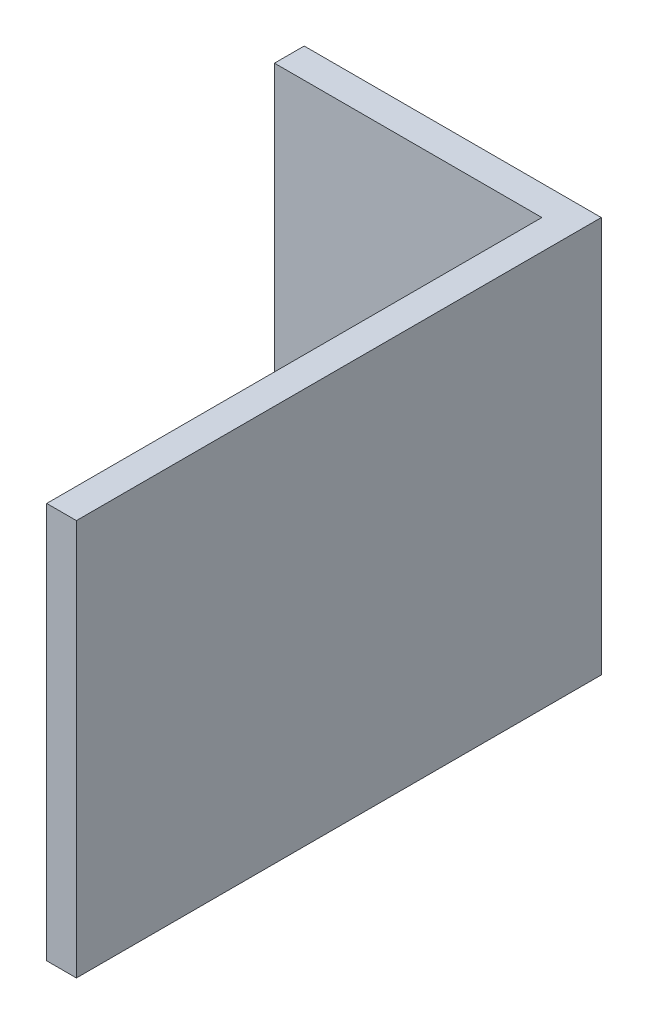
SolidWorks part; units mm, degrees
ref_plane "Plano frontal" through (0, 0, 0) normal (0, 0, 1) x (1, 0, 0)
ref_plane "Plano superior" through (0, 0, 0) normal (0, 1, 0) x (1, 0, 0)
ref_plane "Plano direito" through (0, 0, 0) normal (1, 0, 0) x (0, 0, -1)
sketch "Esboço1" plane through (0, 0, 0) normal (0, 1, 0) x (1, 0, 0)
  line L0 (0, 0) -> (30, 0)
  line L1 (30, 0) -> (30, -53)
  line L2 (30, -53) -> (27, -53)
  line L3 (27, -53) -> (27, -3)
  line L4 (27, -3) -> (0, -3)
  line L5 (0, -3) -> (0, 0)
  dimension "D1" = 3
  dimension "D2" = 3
  dimension "D3" = 50
  dimension "D4" = 30
extrude "Ressalto-extrusão1" add sketch "Esboço1" along normal blind 40
equation "\"D2@Esboço1\"=\"D1@Esboço1\""
